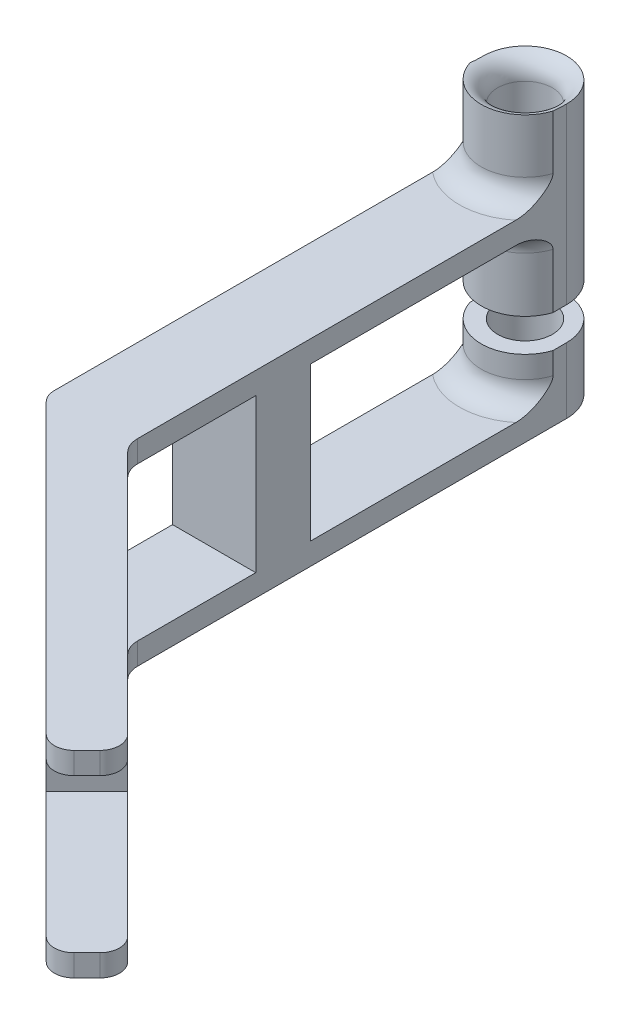
SolidWorks part; units mm, degrees
material "ABS"
ref_plane "Front Plane" through (0, 0, 0) normal (0, 0, 1) x (1, 0, 0)
ref_plane "Top Plane" through (0, 0, 0) normal (0, 1, 0) x (1, 0, 0)
ref_plane "Right Plane" through (0, 0, 0) normal (1, 0, 0) x (0, 0, -1)
sketch "Sketch1" plane through (0, 0, 0) normal (0, 1, 0) x (1, 0, 0)
  circle A0 centre (0, 0) radius 30
  dimension "D1" = 60
extrude "Boss-Extrude1" add sketch "Sketch1" along normal blind 200
sketch "Sketch2" plane through (0, 200, 0) normal (0, 1, 0) x (1, 0, 0)
  circle A0 centre (0, -50) radius 4
  circle A2 centre (0, 0) radius 30 construction
  dimension "D1" = 8
  dimension "D2" = 50
extrude "Boss-Extrude2" add sketch "Sketch2" against normal blind 80 from offset 60 separate body offset against normal yes
sketch "Sketch4" plane through (0, 140, 0) normal (0, 1, 0) x (1, 0, 0)
  line L6 (-2.9328, -47.28) -> (40.9159, 0)
  line L7 (2.9328, -52.72) -> (51.8267, 0)
  line L8 (40.9159, 0) -> (6, 37.6481)
  line L9 (51.8267, 0) -> (11.8657, 43.0881)
  line L10 (6, 37.6481) -> (11.8657, 43.0881)
  circle A0 centre (0, -50) radius 4 construction
  circle A1 centre (0, 0) radius 30 construction
  arc A2 (2.9328, -52.72) -> (-2.9328, -47.28) centre (0, -50) ccw
  dimension "D2" = 6
  dimension "D4" = 8
  dimension "D5" = 8
  dimension "D6" = 8
extrude "Boss-Extrude3" add sketch "Sketch4" against normal blind 10 from offset 10 offset against normal yes
sketch "Sketch5" plane through (0, 60, 0) normal (0, -1, 0) x (1, 0, 0)
  line L0 (6, -37.6481) -> (11.8657, -43.0881) construction
  line L1 (40.9159, 0) -> (6, -37.6481) construction
  line L2 (51.8267, 0) -> (11.8657, -43.0881) construction
  line L3 (2.9328, 52.72) -> (51.8267, 0) construction
  line L4 (-2.9328, 47.28) -> (40.9159, 0) construction
  line L5 (6, -37.6481) -> (11.8657, -43.0881)
  line L6 (40.9159, 0) -> (6, -37.6481)
  line L7 (51.8267, 0) -> (11.8657, -43.0881)
  line L8 (2.9328, 52.72) -> (51.8267, 0)
  line L9 (-2.9328, 47.28) -> (40.9159, 0)
  arc A0 (-2.9328, 47.28) -> (2.9328, 52.72) centre (0, 50) ccw construction
  arc A1 (-2.9328, 47.28) -> (2.9328, 52.72) centre (0, 50) ccw
extrude "Boss-Extrude4" add sketch "Sketch5" against normal blind 10 from offset 10 offset against normal yes
sketch "Sketch7" plane through (0, 140, 0) normal (0, 1, 0) x (1, 0, 0)
  circle A0 centre (0, -50) radius 4
extrude "Cut-Extrude1" cut sketch "Sketch7" against normal blind 12 from offset 34 offset against normal yes
sketch "Sketch8" plane through (0, 140, 0) normal (0, 1, 0) x (1, 0, 0)
  circle A0 centre (0, -50) radius 2
  dimension "D1" = 4
extrude "Cut-Extrude2" cut sketch "Sketch8" against normal blind 70
sketch "Sketch9" plane through (0, 140, 0) normal (0, 1, 0) x (1, 0, 0)
  circle A0 centre (0, -50) radius 2
extrude "Boss-Extrude6" add sketch "Sketch9" against normal blind 70 from offset 0.1
sketch "Sketch11" plane through (0, 140.1, 0) normal (0, 1, 0) x (1, 0, 0)
  line L0 (-0.975, -51.7462) -> (-0.975, -48.2538)
  line L1 (0.975, -48.2538) -> (0.975, -51.7462)
  circle A0 centre (0, -50) radius 2 construction
  circle A1 centre (0, -50) radius 2 construction
  arc A2 (-0.975, -48.2538) -> (-0.975, -51.7462) centre (0, -50) ccw
  arc A3 (0.975, -48.2538) -> (0.975, -51.7462) centre (0, -50) cw
  dimension "D3" = 2
  dimension "D4" = 2
  dimension "D1" = 1.95
  dimension "D2" = 0.975
extrude "Cut-Extrude4" cut sketch "Sketch11" against normal blind 35 from offset 30 offset against normal yes
sketch "Sketch12" plane through (0, 140.1, 0) normal (0, 1, 0) x (1, 0, 0)
  line L1 (-0.5, -48.8) -> (0.5, -48.8)
  line L2 (-0.5, -48.8) -> (-0.5, -51.2)
  line L3 (-0.5, -51.2) -> (0.5, -51.2)
  line L4 (0.5, -48.8) -> (0.5, -51.2)
  dimension "D1" = 0.5
  dimension "D2" = 0.5
  dimension "D3" = 1.2
  dimension "D4" = 2.4
extrude "Cut-Extrude5" cut sketch "Sketch12" against normal blind 20
sketch "Sketch14" plane through (0, 200, 0) normal (0, 1, 0) x (1, 0, 0)
  circle A0 centre (0, 0) radius 30
extrude "Cut-Extrude6" cut sketch "Sketch14" against normal blind 200
sketch "Sketch15" plane through (0, 140, 0) normal (0, 1, 0) x (1, 0, 0)
  circle A0 centre (0, -50) radius 2
extrude "Cut-Extrude7" cut sketch "Sketch15" against normal blind 70 and the other way blind 200
sketch "Sketch18" plane through (0, 130, 0) normal (0, 1, 0) x (1, 0, 0)
  line L5 (2.9328, -52.72) -> (51.8267, 0)
  line L6 (51.8267, 0) -> (11.8657, 43.0881)
  line L7 (11.8657, 43.0881) -> (6, 37.6481)
  line L8 (6, 37.6481) -> (40.9159, 0)
  line L9 (40.9159, 0) -> (-2.9328, -47.28)
  line L10 (2.9328, -52.72) -> (51.8267, 0)
  line L11 (51.8267, 0) -> (11.8657, 43.0881)
  line L12 (11.8657, 43.0881) -> (6, 37.6481)
  line L13 (6, 37.6481) -> (40.9159, 0)
  line L14 (40.9159, 0) -> (-2.9328, -47.28)
  arc A1 (2.9328, -52.72) -> (-2.9328, -47.28) centre (0, -50) ccw
  arc A2 (2.9328, -52.72) -> (-2.9328, -47.28) centre (0, -50) ccw
  dimension "D1" = 0
extrude "Cut-Extrude9" cut sketch "Sketch18" against normal blind 5
sketch "Sketch20" plane through (0, 125, 0) normal (0, 1, 0) x (1, 0, 0)
  line L5 (2.9328, -52.72) -> (51.8267, 0)
  line L6 (51.8267, 0) -> (11.8657, 43.0881)
  line L7 (11.8657, 43.0881) -> (6, 37.6481)
  line L8 (6, 37.6481) -> (40.9159, 0)
  line L9 (40.9159, 0) -> (-2.9328, -47.28)
  line L10 (2.9328, -52.72) -> (51.8267, 0)
  line L11 (51.8267, 0) -> (11.8657, 43.0881)
  line L12 (11.8657, 43.0881) -> (6, 37.6481)
  line L13 (6, 37.6481) -> (40.9159, 0)
  line L14 (40.9159, 0) -> (-2.9328, -47.28)
  arc A1 (2.9328, -52.72) -> (-2.9328, -47.28) centre (0, -50) ccw
  arc A2 (2.9328, -52.72) -> (-2.9328, -47.28) centre (0, -50) ccw
  dimension "D1" = 0
extrude "Cut-Extrude10" cut sketch "Sketch20" against normal blind 5
ref_plane "Plane1" through (0, 100, 0) normal (0, 1, 0) x (1, 0, 0)
sketch "Sketch22" plane through (0, 80, 0) normal (0, 1, 0) x (1, 0, 0)
  line L6 (6, 37.6481) -> (40.9159, 0)
  line L7 (40.9159, 0) -> (-2.9328, -47.28)
  line L8 (2.9328, -52.72) -> (51.8267, 0)
  line L9 (51.8267, 0) -> (11.8657, 43.0881)
  line L10 (11.8657, 43.0881) -> (6, 37.6481)
  line L11 (6, 37.6481) -> (40.9159, 0)
  line L12 (40.9159, 0) -> (-2.9328, -47.28)
  line L13 (2.9328, -52.72) -> (51.8267, 0)
  line L14 (51.8267, 0) -> (11.8657, 43.0881)
  line L15 (11.8657, 43.0881) -> (6, 37.6481)
  arc A1 (2.9328, -52.72) -> (-2.9328, -47.28) centre (0, -50) ccw
  arc A2 (2.9328, -52.72) -> (-2.9328, -47.28) centre (0, -50) ccw
  dimension "D1" = 0
extrude "Cut-Extrude11" cut sketch "Sketch22" against normal blind 10
sketch "Sketch24" plane through (0, 60, 0) normal (0, -1, 0) x (1, 0, 0)
  circle A0 centre (0, 50) radius 4 construction
  circle A1 centre (0, 50) radius 4
extrude "Cut-Extrude12" cut sketch "Sketch24" against normal blind 10
sketch "Sketch25" plane through (0, 140, 0) normal (0, 1, 0) x (1, 0, 0)
  circle A0 centre (0, -50) radius 4 construction
  circle A1 centre (0, -50) radius 4
extrude "Cut-Extrude13" cut sketch "Sketch25" against normal blind 10
fillet "Fillet10" radius 2 1 edges at (0, 130, 52)
sketch "Sketch28" plane through (0, 70, 0) normal (0, -1, 0) x (1, 0, 0)
  line L1 (-7.7664, 66.8906) -> (11.2683, 66.8906)
  line L2 (-7.7664, 66.8906) -> (-7.7664, 36.4785)
  line L3 (-7.7664, 36.4785) -> (11.2683, 36.4785)
  line L4 (11.2683, 66.8906) -> (11.2683, 36.4785)
extrude "Cut-Extrude14" cut sketch "Sketch28" against normal blind 30
sketch "Sketch30" plane through (0, 106, 0) normal (0, -1, 0) x (1, 0, 0)
  line L1 (-4, 50) -> (4, 50)
  line L2 (-4, 50) -> (-4, 90)
  line L4 (4, 50) -> (4, 90)
  line L9 (-4, 90) -> (4, 90)
  line L10 (-4, 90) -> (24.2843, 118.2843)
  line L11 (4, 90) -> (28.2843, 114.2843)
  line L12 (24.2843, 118.2843) -> (28.2843, 114.2843)
  circle A0 centre (0, 50) radius 4 construction
  dimension "D1" = 8
  dimension "D2" = 40
  dimension "D3" = 135
  dimension "D4" = 40
extrude "Boss-Extrude7" add sketch "Sketch30" along normal blind 2 from offset 15 contours L12 L10 L9 L11 | L9 L4 L1 L2 region at (13.066, 106, 103.1675) offset against normal yes
sketch "Sketch31" plane through (0, 106, 0) normal (0, -1, 0) x (1, 0, 0)
  line L1 (-11.9647, 54.8867) -> (12.9558, 54.8867)
  line L2 (-11.9647, 54.8867) -> (-11.9647, 44.889)
  line L3 (-11.9647, 44.889) -> (12.9558, 44.889)
  line L4 (12.9558, 54.8867) -> (12.9558, 44.889)
extrude "Cut-Extrude15" cut sketch "Sketch31" against normal blind 6
sketch "Sketch32" plane through (0, 112, 0) normal (0, -1, 0) x (1, 0, 0)
  arc A0 (2, 50) -> (-2, 50) centre (0, 50) ccw construction
  circle A1 centre (0, 50) radius 4 construction
  circle A2 centre (0, 50) radius 2 construction
  circle A3 centre (0, 50) radius 4
  circle A4 centre (0, 50) radius 2
  arc A5 (2, 50) -> (-2, 50) centre (0, 50) ccw
  circle M1 centre (0, 50) radius 4
  circle M2 centre (0, 50) radius 2
extrude "Boss-Extrude8" add sketch "Sketch32" along normal blind 6 from offset 3 separate body contours A4 M1 M2 region at (-3.8869, 112, 50)
sketch "Sketch33" plane through (0, 103, 0) normal (0, -1, 0) x (1, 0, 0)
  line L0 (-2, 50) -> (2, 50) construction
  circle A0 centre (0, 50) radius 2
extrude "Boss-Extrude9" add sketch "Sketch33" against normal blind 2
sketch "Sketch34" plane through (0, 103, 0) normal (0, -1, 0) x (1, 0, 0)
  line L0 (4, 50) -> (4, 90) construction
  line L1 (4, 90) -> (28.2843, 114.2843) construction
  line L2 (24.2843, 118.2843) -> (28.2843, 114.2843) construction
  line L3 (-4, 90) -> (24.2843, 118.2843) construction
  line L4 (-4, 50) -> (-4, 90) construction
  line L5 (4, 50) -> (4, 90)
  line L6 (4, 90) -> (28.2843, 114.2843)
  line L7 (24.2843, 118.2843) -> (28.2843, 114.2843)
  line L8 (-4, 90) -> (24.2843, 118.2843)
  line L9 (-4, 50) -> (-4, 90)
  circle M1 centre (0, 50) radius 4
extrude "Boss-Extrude10" add sketch "Sketch34" against normal blind 2 contours L9 L5 L6 L7 L8 M1 region at (0, 103, 54.7553)
sketch "Sketch35" plane through (0, 121, 0) normal (0, 1, 0) x (1, 0, 0)
  line L0 (-2, -50) -> (2, -50) construction
  circle A0 centre (0, -50) radius 2
extrude "Cut-Extrude16" cut sketch "Sketch35" against normal blind 2
sketch "Sketch36" plane through (0, 119, 0) normal (0, -1, 0) x (1, 0, 0)
  line L3 (-4, 50) -> (-4, 90) construction
  line L4 (-4, 73.3857) -> (4, 73.3857)
  line L5 (-4, 73.3857) -> (-4, 78.3857)
  line L6 (-4, 78.3857) -> (4, 78.3857)
  line L7 (4, 73.3857) -> (4, 78.3857)
  line L8 (4, 50) -> (4, 90) construction
  line L9 (11.3773, 97.3773) -> (7.3773, 101.3773)
  line L10 (4, 90) -> (28.2843, 114.2843) construction
  line L11 (-4, 90) -> (24.2843, 118.2843) construction
  line L12 (7.3773, 101.3773) -> (11.3795, 105.3795)
  line L13 (11.3795, 105.3795) -> (15.3795, 101.3795)
  line L14 (15.3795, 101.3795) -> (11.3773, 97.3773)
  dimension "D1" = 5.66
  dimension "D2" = 5
extrude "Boss-Extrude11" add sketch "Sketch36" along normal blind 14
fillet "Fillet11" radius 2 11 edges at (0, 105, 54) (0, 119, 54) (0, 121, 54) (-4, 120, 90) (-4, 104, 90) (4, 104, 90) (4, 120, 90) (28.2843, 104, 114.2843) (24.2843, 104, 118.2843) (24.2843, 120, 118.2843) (28.2843, 120, 114.2843)
sketch "Sketch37" plane through (0, 121, 0) normal (0, 1, 0) x (1, 0, 0)
  line L0 (4, -54.4721) -> (4, -50) construction
  line L1 (-4, -50) -> (-4, -54.4721) construction
  line L2 (4, -54.4721) -> (4, -89.1716) construction
  line L3 (-4, -54.4721) -> (-4, -89.1716) construction
  line L4 (-3.4142, -90.5858) -> (22.8701, -116.8701) construction
  line L5 (25.6985, -116.8701) -> (26.8701, -115.6985) construction
  line L6 (4.5858, -90.5858) -> (26.8701, -112.8701) construction
  line L7 (4, -54.4721) -> (4, -50)
  line L8 (-4, -50) -> (-4, -54.4721)
  line L9 (4, -54.4721) -> (4, -89.1716)
  line L10 (-4, -54.4721) -> (-4, -89.1716)
  line L11 (-3.4142, -90.5858) -> (22.8701, -116.8701)
  line L12 (25.6985, -116.8701) -> (26.8701, -115.6985)
  line L13 (4.5858, -90.5858) -> (26.8701, -112.8701)
  line L14 (3.8, -54.4721) -> (3.8, -50)
  line L15 (-3.8, -50) -> (-3.8, -54.4721)
  line L16 (-3.8, -54.4721) -> (-3.8, -89.1716)
  line L17 (-3.2728, -90.4444) -> (23.0115, -116.7286)
  line L18 (25.5571, -116.7286) -> (26.7286, -115.5571)
  line L19 (4.4444, -90.7272) -> (26.7286, -113.0115)
  line L20 (3.8, -54.4721) -> (3.8, -89.1716)
  circle A0 centre (0, -50) radius 4 construction
  arc A1 (4, -89.1716) -> (4.5858, -90.5858) centre (6, -89.1716) ccw construction
  arc A2 (-4, -89.1716) -> (-3.4142, -90.5858) centre (-2, -89.1716) ccw construction
  arc A3 (22.8701, -116.8701) -> (25.6985, -116.8701) centre (24.2843, -115.4558) ccw construction
  arc A4 (26.8701, -115.6985) -> (26.8701, -112.8701) centre (25.4558, -114.2843) ccw construction
  arc A5 (4, -50) -> (-4, -50) centre (0, -50) ccw
  arc A6 (4, -89.1716) -> (4.5858, -90.5858) centre (6, -89.1716) ccw
  arc A7 (-4, -89.1716) -> (-3.4142, -90.5858) centre (-2, -89.1716) ccw
  arc A8 (22.8701, -116.8701) -> (25.6985, -116.8701) centre (24.2843, -115.4558) ccw
  arc A9 (26.8701, -115.6985) -> (26.8701, -112.8701) centre (25.4558, -114.2843) ccw
  arc A10 (3.8, -50) -> (-3.8, -50) centre (0, -50) ccw
  arc A11 (-3.8, -89.1716) -> (-3.2728, -90.4444) centre (-2, -89.1716) ccw
  arc A12 (23.0115, -116.7286) -> (25.5571, -116.7286) centre (24.2843, -115.4558) ccw
  arc A13 (26.7286, -115.5571) -> (26.7286, -113.0115) centre (25.4558, -114.2843) ccw
  arc A14 (3.8, -89.1716) -> (4.4444, -90.7272) centre (6, -89.1716) ccw
  dimension "D1" = 0.2
extrude "Cut-Extrude17" cut sketch "Sketch37" against normal blind 60 and the other way blind 50
sketch "Sketch38" plane through (0, 105, 0) normal (0, 1, 0) x (1, 0, 0)
  circle A0 centre (0, -50) radius 2
  circle A1 centre (0, -50) radius 2.5
  circle M2 centre (0, -50) radius 2
  dimension "D1" = 5
extrude "Cut-Extrude18" cut sketch "Sketch38" along normal blind 40 contours A1 M2 region at (-2.4293, 105, 50)
sketch "Sketch41" plane through (0, 121, 0) normal (0, 1, 0) x (1, 0, 0)
  line L1 (-12.3305, -40.2112) -> (17.9281, -40.2112)
  line L2 (-12.3305, -40.2112) -> (-12.3305, -63.0215)
  line L3 (-12.3305, -63.0215) -> (17.9281, -63.0215)
  line L4 (17.9281, -40.2112) -> (17.9281, -63.0215)
extrude "Cut-Extrude20" cut sketch "Sketch41" along normal blind 30 from offset 7
fillet "Fillet12" radius 2 1 edges at (0, 128, 52.5)
sketch "Sketch42" plane through (0, 119, 0) normal (0, -1, 0) x (1, 0, 0)
  line L0 (-3.8, 73.3857) -> (3.8, 73.3857) construction
  circle A0 centre (0, 66.3857) radius 2
  dimension "D1" = 4
  dimension "D2" = 7
extrude "Boss-Extrude12" add sketch "Sketch42" along normal blind 1.3
